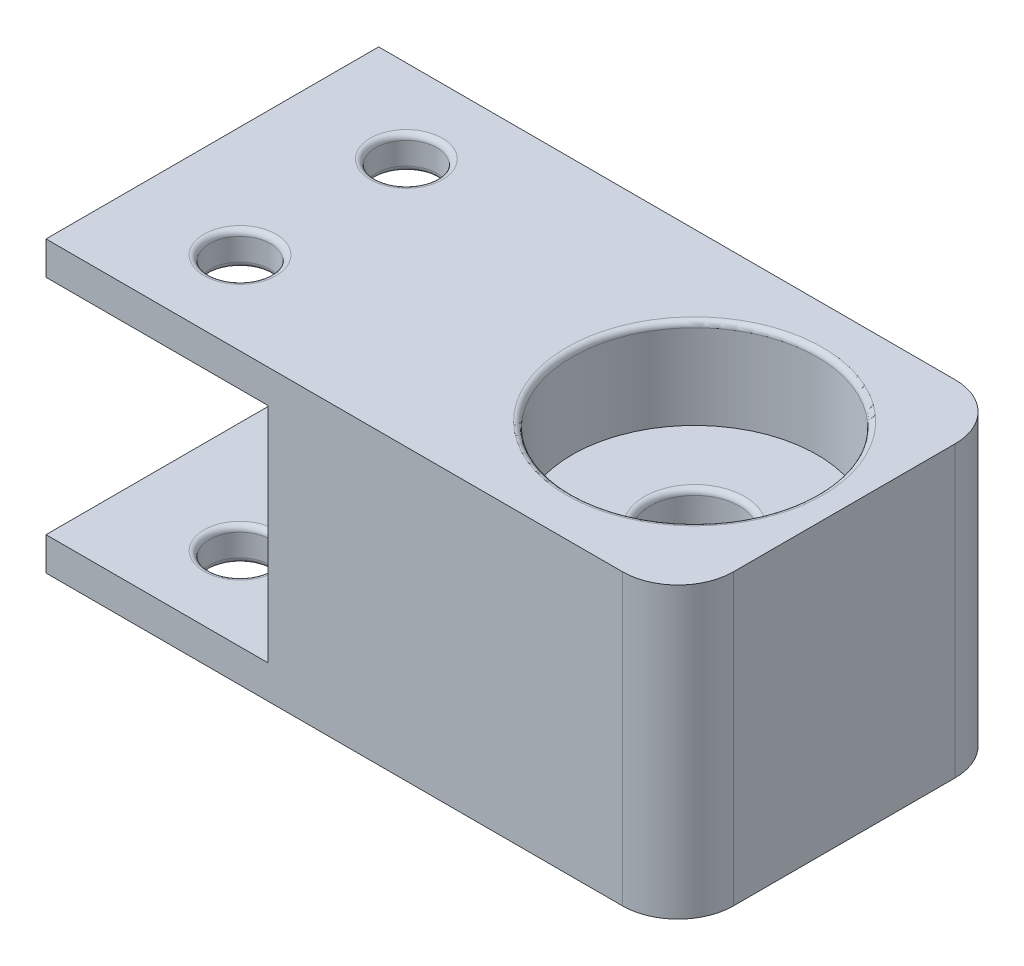
SolidWorks part; units mm, degrees
ref_plane "Front Plane" through (0, 0, 0) normal (0, 0, 1) x (1, 0, 0)
ref_plane "Top Plane" through (0, 0, 0) normal (0, 1, 0) x (1, 0, 0)
ref_plane "Right Plane" through (0, 0, 0) normal (1, 0, 0) x (0, 0, -1)
sketch "Sketch4" plane through (0, 0, 0) normal (0, 1, 0) x (1, 0, 0)
  line L1 (-28.5, -15) -> (28.5, -15)
  line L2 (-28.5, -15) -> (-28.5, 15)
  line L3 (-28.5, 15) -> (28.5, 15)
  line L4 (28.5, -15) -> (28.5, 15)
  line L5 (-28.5, -15) -> (28.5, 15) construction
  line L6 (-28.5, 15) -> (28.5, -15) construction
  point P0 (0, 0)
  dimension "D1" = 57
  dimension "D2" = 30
extrude "Boss-Extrude2" add sketch "Sketch4" along normal blind 3
sketch "Sketch5" plane through (0, 3, 0) normal (0, 1, 0) x (1, 0, 0)
  line L0 (-28.5, -15) -> (28.5, -15) construction
  line L1 (28.5, 15) -> (-8.5, 15)
  line L2 (28.5, 15) -> (28.5, -15)
  line L3 (28.5, -15) -> (-8.5, -15)
  line L4 (-8.5, 15) -> (-8.5, -15)
  line L5 (28.5, 15) -> (-8.5, -15) construction
  line L6 (28.5, -15) -> (-8.5, 15) construction
  line L7 (-28.5, 15) -> (-28.5, -15) construction
  point P4 (10, 0)
  dimension "D1" = 20
extrude "Boss-Extrude3" add sketch "Sketch5" along normal blind 20.1
sketch "Sketch6" plane through (0, 23.1, 0) normal (0, 1, 0) x (1, 0, 0)
  line L0 (28.5, -15) -> (28.5, 15) construction
  line L1 (28.5, 15) -> (-8.5, 15) construction
  line L3 (-8.5, -15) -> (28.5, -15) construction
  line L5 (-8.5, 15) -> (-28.5, 15) construction
  line L6 (-28.5, 15) -> (-28.5, -15) construction
  line L7 (-28.5, -15) -> (-8.5, -15) construction
  line L8 (28.5, -15) -> (28.5, 15)
  line L9 (28.5, 15) -> (-8.5, 15)
  line L11 (-8.5, -15) -> (28.5, -15)
  line L13 (-8.5, 15) -> (-28.5, 15)
  line L14 (-28.5, 15) -> (-28.5, -15)
  line L15 (-28.5, -15) -> (-8.5, -15)
extrude "Boss-Extrude4" add sketch "Sketch6" along normal blind 3
sketch "Sketch7" plane through (0, 26.1, 0) normal (0, 1, 0) x (1, 0, 0)
  line L0 (-28.5, -15) -> (28.5, -15) construction
  line L1 (-28.5, 15) -> (-28.5, -15) construction
  line L2 (-28.5, 0) -> (28.5, 0) construction
  line L3 (28.5, -15) -> (28.5, 15) construction
  circle A0 centre (-18.5, -7.5) radius 2.75
  circle A1 centre (-18.5, 7.5) radius 2.75
  dimension "D1" = 5.5
  dimension "D2" = 7.5
  dimension "D3" = 10
extrude "Cut-Extrude3" cut sketch "Sketch7" against normal through all
fillet "Fillet5" radius 0.5 8 edges at (-18.5, 3, -10.25) (-18.5, 0, -10.25) (-18.5, 3, 4.75) (-18.5, 0, 10.25) (-18.5, 23.1, -4.75) (-18.5, 26.1, -10.25) (-18.5, 23.1, 10.25) (-18.5, 26.1, 10.25)
sketch "Sketch8" plane through (0, 26.1, 0) normal (0, 1, 0) x (1, 0, 0)
  line L0 (-8.5, 15) -> (-8.5, -15) construction
  line L1 (-8.5, 15) -> (-8.5, -15) construction
  line L2 (28.5, -15) -> (28.5, 15) construction
  circle A1 centre (15, 0) radius 11.049
  point P4 (10, 5.4235)
  point P5 (0, 0)
  point P8 (0, 0)
  point P9 (0, 0)
  dimension "D1" = 22.098
  dimension "D2" = 13.5
extrude "Cut-Extrude4" cut sketch "Sketch8" against normal blind 8.128 contours A1
fillet "Fillet6" radius 5 2 edges at (28.5, 13.05, -15) (28.5, 13.05, 15)
sketch "Sketch11" plane through (0, 0, 0) normal (0, -1, 0) x (1, 0, 0)
  circle A1 centre (15, 0) radius 11.049 construction
  circle A2 centre (15, 0) radius 11.049
extrude "Cut-Extrude5" cut sketch "Sketch11" against normal blind 8.128
sketch "Sketch12" plane through (0, 8.128, 0) normal (0, -1, 0) x (1, 0, 0)
  circle A0 centre (15, 0) radius 4.025
  circle A1 centre (15, 0) radius 11.049
  circle A4 centre (15, 0) radius 11.049
  point P1 (0, 0)
  point P5 (0, 0)
  dimension "D2" = 8.05
  dimension "D1" = 0
extrude "Cut-Extrude6" cut sketch "Sketch12" against normal through all contours A0 region at (15, 8.128, 0)
fillet "Fillet7" radius 0.5 4 edges at (15, 26.1, 11.049) (15, 8.128, -4.025) (15, 17.972, 4.025) (15, 0, -11.049)
